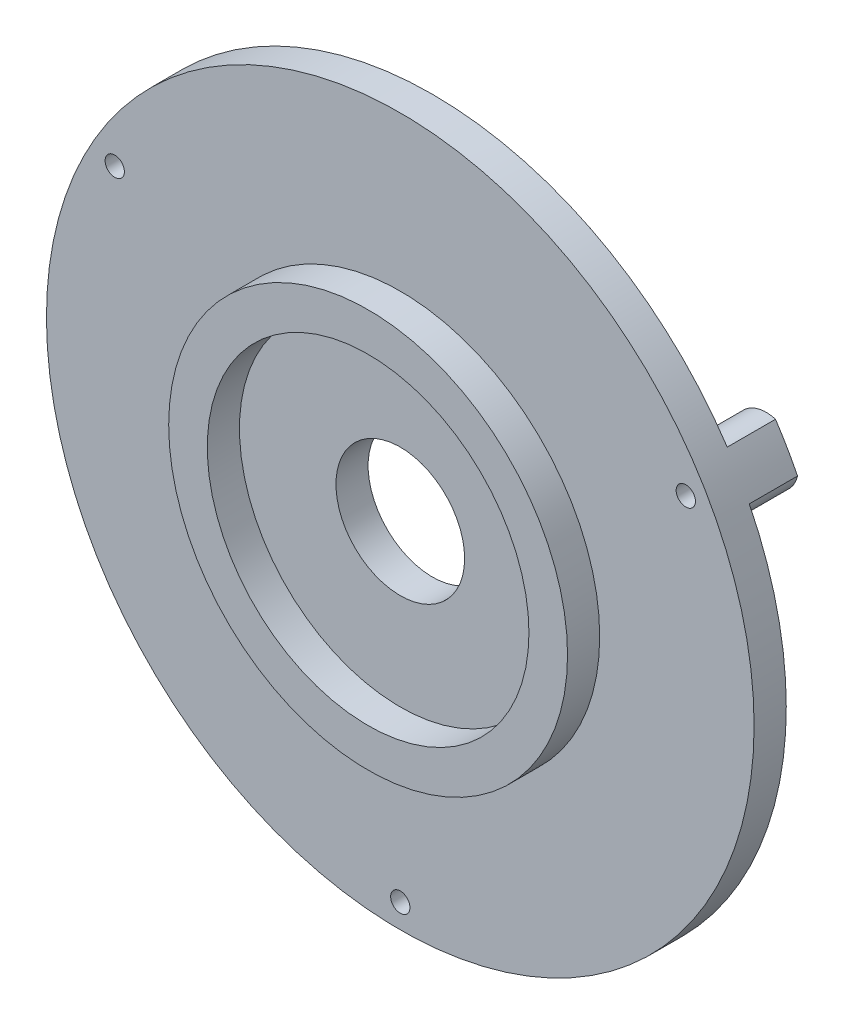
SolidWorks part; units mm, degrees
ref_plane "前视基准面" through (0, 0, 0) normal (0, 0, 1) x (1, 0, 0)
ref_plane "上视基准面" through (0, 0, 0) normal (0, 1, 0) x (1, 0, 0)
ref_plane "右视基准面" through (0, 0, 0) normal (1, 0, 0) x (0, 0, -1)
sketch "草图1" plane through (0, 0, 0) normal (0, 0, 1) x (1, 0, 0)
  circle A0 centre (0, 0) radius 22
extrude "凸台-拉伸1" add sketch "草图1" along normal blind 2
sketch "草图2" plane through (0, 0, 2) normal (0, 0, 1) x (1, 0, 0)
  circle A0 centre (0, 0) radius 12.4
  circle A1 centre (0, 0) radius 10
extrude "凸台-拉伸2" add sketch "草图2" along normal blind 2
sketch "草图3" plane through (0, 0, 2) normal (0, 0, 1) x (1, 0, 0)
  circle A0 centre (0, 0) radius 4
extrude "切除-拉伸1" cut sketch "草图3" against normal blind 11
sketch "草图4" plane through (0, 0, 0) normal (0, 0, -1) x (-1, 0, 0)
  line L0 (0, 0) -> (0, -20.5) construction
  arc A1 (1.3698, -21.9573) -> (-1.3698, -21.9573) centre (0, -20.5) ccw
  arc A2 (-19.7005, 9.7924) -> (-18.3307, 12.1649) centre (-17.7535, 10.25) ccw
  arc A3 (18.3307, 12.1649) -> (19.7005, 9.7924) centre (17.7535, 10.25) ccw
  arc A4 (-1.3698, -21.9573) -> (1.3698, -21.9573) centre (0, 0) ccw
  arc A5 (-18.3307, 12.1649) -> (-19.7005, 9.7924) centre (0, 0) ccw
  arc A6 (19.7005, 9.7924) -> (18.3307, 12.1649) centre (0, 0) ccw
  dimension "D1" = 3
  dimension "D2" = 20.5
extrude "凸台-拉伸3" add sketch "草图4" along normal blind 3
sketch "草图5" plane through (0, 0, -3) normal (0, 0, -1) x (-1, 0, 0)
  circle A1 centre (0, -20.5) radius 0.6
  circle A2 centre (-17.7535, 10.25) radius 0.6
  circle A3 centre (17.7535, 10.25) radius 0.6
extrude "切除-拉伸2" cut sketch "草图5" against normal blind 16
